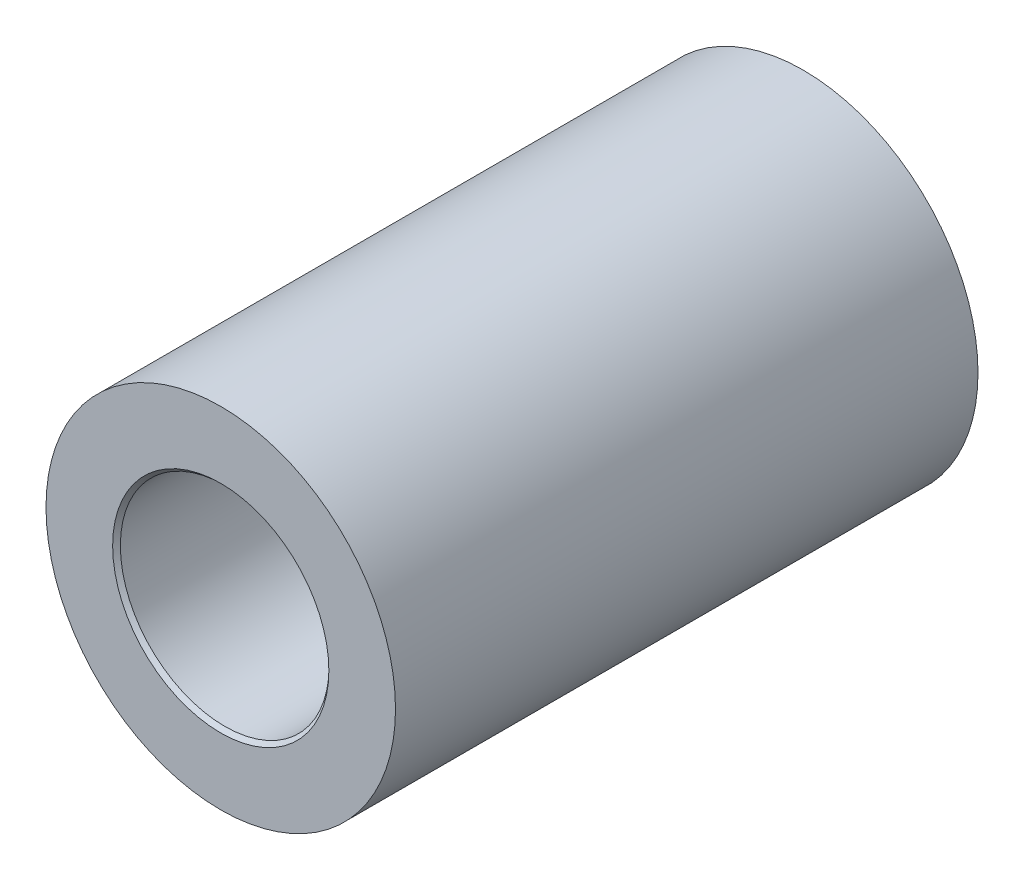
SolidWorks part; units mm, degrees
ref_plane "Front Plane" through (0, 0, 0) normal (0, 0, 1) x (1, 0, 0)
ref_plane "Top Plane" through (0, 0, 0) normal (0, 1, 0) x (1, 0, 0)
ref_plane "Right Plane" through (0, 0, 0) normal (1, 0, 0) x (0, 0, -1)
sketch "Sketch3" plane through (0, 0, 0) normal (1, 0, 0) x (0, 0, -1)
  line L0 (-3.9688, 0) -> (3.9688, 0) construction
  line L1 (0, 3.175) -> (0, -3.175) construction
  line L2 (-3.9688, 1.4224) -> (-3.9688, -1.4224) construction
  point P2 (-8.7312, 0)
  point P3 (8.7312, 0)
  dimension "D1" = 12.7
  dimension "Length" = 7.9375
  dimension "Min Thread Length" = 12.7
  dimension "Thread Dia" = 2.8448
  dimension "OD" = 6.35
sketch "Sketch1" plane through (0, 0, 0) normal (0, 0, 1) x (1, 0, 0)
  circle A1 centre (0, 0) radius 1.4224
  circle A2 centre (0, 0) radius 3.175
extrude "Extrude1" add sketch "Sketch1" along normal up to vertex (3.9688 mm away) and the other way up to vertex (3.9688 mm away) up to point (0, 0, 3.9688) other way up to point (0, 0, -3.9688)
sketch "Sketch11" plane through (0, 0, -3.9688) normal (0, 0, -1) x (-1, 0, 0)
  circle A0 centre (0, 0) radius 1.4224 construction
  circle A1 centre (0, 0) radius 1.4224
curve "Helix/Spiral1" pitch 0.635 height 8.5725 turns 13.5 parameters "Pitch"=0.635
sketch "Sketch12" plane through (0, 0, 0) normal (1, 0, 0) x (0, 0, -1)
  line L0 (4.5244, 1.4224) -> (3.9688, 1.4224)
  line L1 (4.5244, 1.4224) -> (4.2862, 1.01)
  line L2 (4.2862, 1.01) -> (4.2069, 1.01)
  line L3 (4.2069, 1.01) -> (3.9688, 1.4224)
  line L4 (4.2466, 1.01) -> (4.2466, 1.4224) construction
  line L5 (4.4053, 1.2162) -> (4.0878, 1.2162) construction
  dimension "D1" = 0.0794
  dimension "D2" = 0.3175
  dimension "D3" = 60
sweep "Sweep1" [suppressed] add profiles "Sketch12" path "Helix/Spiral1"
sketch "Sketch6" plane through (0, 0, -3.9688) normal (0, 0, -1) x (-1, 0, 0)
  circle A1 centre (0, 0) radius 3.175
  circle A2 centre (0, 0) radius 3.175
  dimension "D1" = 0
extrude "Extrude2" [suppressed] cut sketch "Sketch6" along normal through all
sketch "Sketch7" plane through (0, 0, -3.9688) normal (0, 0, -1) x (-1, 0, 0)
  circle A2 centre (0, 0) radius 1.4732
  circle A3 centre (0, 0) radius 1.4732
  dimension "D1" = 0.0508
extrude "Extrude3" cut sketch "Sketch7" against normal through all draft 43
mirror "Mirror1" about plane through (0, 0, 0) normal (0, 0, 1) of "Extrude2", "Extrude3"
sketch "Sketch9" [suppressed] plane through (0, 0, 0) normal (1, 0, 0) x (0, 0, -1)
  line L1 (-6.35, 1.4732) -> (6.35, 1.4732)
  line L2 (-6.35, 1.4732) -> (-6.35, 0)
  line L3 (-6.35, 0) -> (6.35, 0)
  line L4 (6.35, 1.4732) -> (6.35, 0)
  line L7 (-12.7, 0) -> (12.7, 0) construction
revolve "Revolve" [suppressed] add sketch "Sketch9" angle 360 about L0
sketch "Sketch10" [suppressed] plane through (0, 0, 0) normal (1, 0, 0) x (0, 0, -1)
  line L0 (12.7, 1.4224) -> (6.35, 1.4224)
  line L1 (-12.7, 1.4224) -> (-6.35, 1.4224)
  line L2 (6.35, 1.4224) -> (6.35, -1.4224)
  line L3 (-12.7, -1.4732) -> (-6.35, -1.4732)
  line L4 (-6.35, 1.4224) -> (-6.35, -1.4732)
  line L5 (6.35, -1.4224) -> (12.7, -1.4224)
sketch "Sketch13" plane through (0, 0, 3.9688) normal (0, 0, 1) x (1, 0, 0)
  circle A0 centre (0, 0) radius 2.3813
  dimension "D1" = 4.7625
extrude "Cut-Extrude1" cut sketch "Sketch13" against normal through all flip side to cut
equation "\"D1@Sketch3\" = \"Min Thread Length@Sketch3\""
equation "\"D3@Helix/Spiral1\" = \"Length@Sketch3\"+\"Pitch@Helix/Spiral1\""
equation "\"D1@Sketch12\" = \"Pitch@Helix/Spiral1\"*.125"
equation "\"D2@Sketch12\" = \"Pitch@Helix/Spiral1\"*.5"
